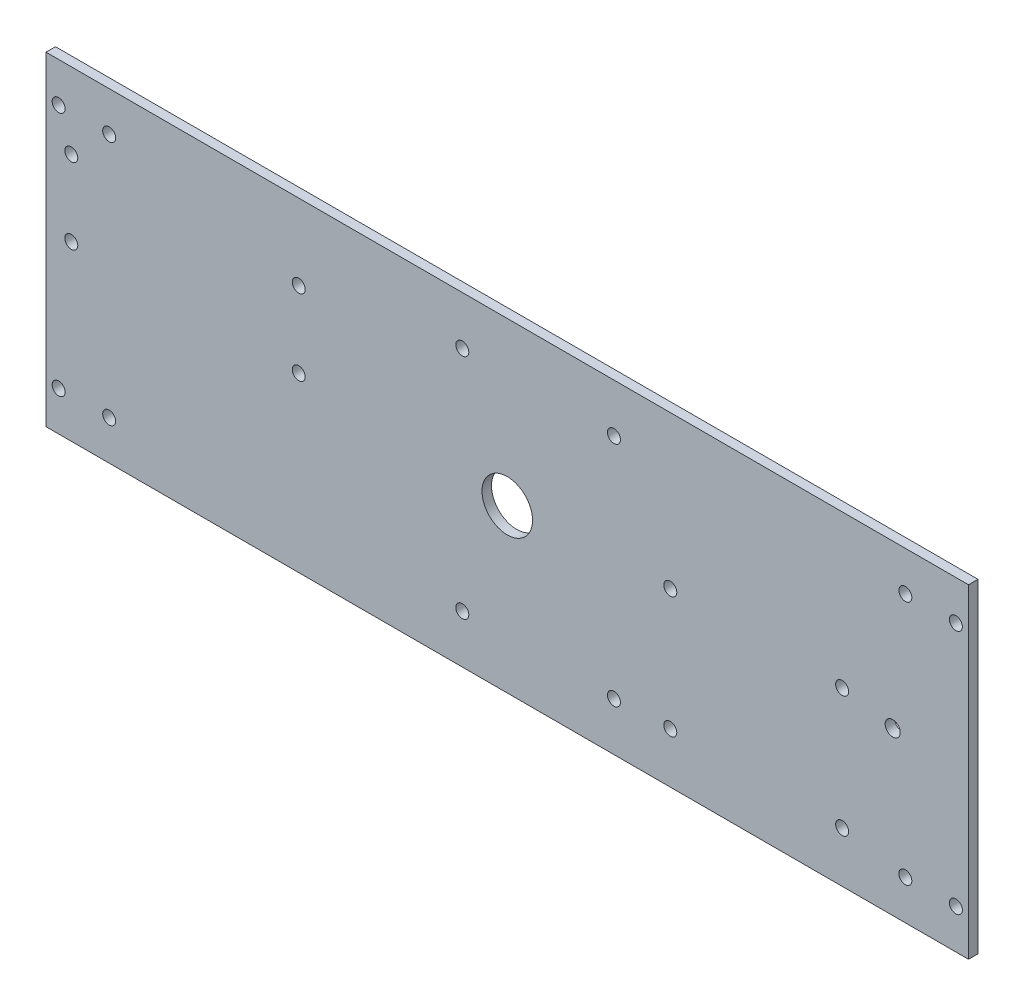
SolidWorks part; units mm, degrees
material "E-Glass Fiber"
ref_plane "Front Plane" through (0, 0, 0) normal (0, 0, 1) x (1, 0, 0)
ref_plane "Top Plane" through (0, 0, 0) normal (0, 1, 0) x (1, 0, 0)
ref_plane "Right Plane" through (0, 0, 0) normal (1, 0, 0) x (0, 0, -1)
sketch "Sketch1" plane through (0, 0, 0) normal (0, 0, 1) x (1, 0, 0)
  line L1 (-115.8875, -40.748) -> (115.8875, -40.748)
  line L2 (-115.8875, -40.748) -> (-115.8875, 40.7479)
  line L3 (-115.8875, 40.7479) -> (115.8875, 40.7479)
  line L4 (115.8875, -40.748) -> (115.8875, 40.7479)
  line L5 (-115.8875, -40.748) -> (115.8875, 40.7479) construction
  line L6 (-115.8875, 40.7479) -> (115.8875, -40.748) construction
  point P0 (0, 0)
  dimension "D1" = 231.775
  dimension "D2" = 81.4959
extrude "Boss-Extrude1" add sketch "Sketch1" along normal blind 2.3813
sketch "Sketch2" plane through (0, 0, 2.3813) normal (0, 0, 1) x (1, 0, 0)
  line L0 (-11.2979, 28.575) -> (26.8021, 28.575) construction
  line L1 (-115.8875, 0) -> (-111.125, 0) construction
  line L2 (115.8875, 0) -> (96.8375, 0) construction
  line L3 (-115.8875, 40.7479) -> (-115.8875, -40.748) construction
  line L4 (-111.125, 0) -> (-111.125, 9.525) construction
  line L5 (-111.125, 9.525) -> (-111.125, 25.4) construction
  line L6 (115.8875, 0) -> (111.125, 0) construction
  line L7 (115.8875, -40.748) -> (115.8875, 40.7479) construction
  line L8 (111.125, 0) -> (111.125, 9.525) construction
  line L9 (111.125, 9.525) -> (111.125, 25.4) construction
  line L10 (-112.7125, 40.7479) -> (-112.7125, 30.8204) construction
  line L11 (115.8875, 40.7479) -> (-115.8875, 40.7479) construction
  line L12 (-112.7125, 30.8204) -> (-100.0125, 30.8204) construction
  line L13 (-112.7125, 30.8204) -> (-115.8875, 30.8204) construction
  dimension "D1" = 38.1
  dimension "D2" = 28.575
  dimension "D3" = 11.2979
  dimension "D4" = 9.525
  dimension "D5" = 25.4
  dimension "D6" = 4.7625
  dimension "D7" = 3.175
  dimension "D8" = 30.8204
  dimension "D9" = 12.7
  dimension "D10" = 19.05
hole_wizard "#4 Clearance Hole1" positions "Sketch4" profile "Sketch5" hole size "#4" standard "ANSI Inch" end condition through all
sketch "Sketch4" plane through (0, 0, 2.3813) normal (0, 0, 1) x (1, 0, 0)
  point P0 (-11.2979, 28.575)
  point P3 (26.8021, 28.575)
sketch "Sketch5" plane through (-11.2979, 28.575, 2.3813) normal (1, 0, 0) x (0, -1, 0)
  line L0 (0, 0) -> (0, 2.3813)
  line L1 (0, 2.3813) -> (1.6319, 2.3813)
  line L2 (1.6319, 2.3813) -> (1.6319, 0)
  line L5 (1.6319, 0) -> (0, 0)
  line L11 (0, -6.35) -> (0, 107.95) construction
  dimension "Thru Hole Dia." = 3.2639
  dimension "Thru Hole Depth" = 2.3813
mirror "Mirror1" about plane through (0, 0, 0) normal (0, 1, 0) of "#4 Clearance Hole1"
hole_wizard "#4 Clearance Hole2" positions "Sketch7" profile "Sketch6" hole size "#4" standard "ANSI Inch"
sketch "Sketch7" plane through (0, 0, 2.3813) normal (0, 0, 1) x (1, 0, 0)
  point P0 (-112.7125, 30.8204)
  point P3 (-100.0125, 30.8204)
sketch "Sketch6" plane through (-112.7125, 30.8204, 2.3813) normal (1, 0, 0) x (0, -1, 0)
  line L0 (0, 0) -> (0, 10.5056)
  line L1 (0, 10.5056) -> (1.6319, 9.525)
  line L2 (1.6319, 9.525) -> (1.6319, 0)
  line L5 (1.6319, 0) -> (0, 0)
  line L10 (0, 10.5056) -> (-1.632, 9.525) construction
  line L11 (0, -6.35) -> (0, 107.95) construction
  dimension "Hole Dia." = 3.2639
  dimension "Hole Depth" = 9.525
  dimension "Drill Angle" = 118
mirror "Mirror2" about plane through (0, 0, 0) normal (1, 0, 0) of "#4 Clearance Hole2"
mirror "Mirror3" about plane through (0, 0, 0) normal (0, 1, 0) of "Mirror2"
hole_wizard "1/2 (0.5) Diameter Hole1" positions "Sketch9" profile "Sketch8" hole size "1/2" standard "ANSI Inch" end condition through all
sketch "Sketch9" plane through (0, 0, 2.3813) normal (0, 0, 1) x (1, 0, 0)
  point P0 (0, 0)
sketch "Sketch8" plane through (0, 0, 2.3813) normal (1, 0, 0) x (0, -1, 0)
  line L0 (0, 0) -> (0, 2.3812)
  line L1 (0, 2.3812) -> (6.35, 2.3812)
  line L2 (6.35, 2.3812) -> (6.35, 0)
  line L5 (6.35, 0) -> (0, 0)
  line L11 (0, -6.35) -> (0, 107.95) construction
  dimension "Thru Hole Dia." = 12.7
  dimension "Thru Hole Depth" = 2.3813
sketch "Sketch10" plane through (0, 0, 2.3813) normal (0, 0, 1) x (1, 0, 0)
  line L0 (-115.8875, 40.7479) -> (-115.8875, -40.748) construction
  line L1 (-109.5375, 21.6979) -> (-52.3875, 21.6979) construction
  line L2 (-109.5375, 21.6979) -> (-109.5375, 2.6479) construction
  line L3 (-109.5375, 2.6479) -> (-52.3875, 2.6479) construction
  line L4 (-52.3875, 21.6979) -> (-52.3875, 2.6479) construction
  line L5 (115.8875, 40.7479) -> (-115.8875, 40.7479) construction
  line L6 (-115.8875, -40.748) -> (115.8875, -40.748) construction
  line L7 (40.9575, -28.048) -> (84.1375, -28.048)
  line L8 (40.9575, -28.048) -> (40.9575, 2.432)
  line L9 (40.9575, 2.432) -> (84.1375, 2.432)
  line L10 (84.1375, -28.048) -> (84.1375, 2.432)
  line L11 (40.9575, -28.048) -> (84.1375, 2.432) construction
  line L12 (40.9575, 2.432) -> (84.1375, -28.048) construction
  line L13 (115.8875, -40.748) -> (115.8875, 40.7479) construction
  point P8 (62.5475, -12.808)
  dimension "D1" = 57.15
  dimension "D2" = 19.05
  dimension "D3" = 6.35
  dimension "D4" = 19.05
  dimension "D5" = 30.48
  dimension "D6" = 43.18
  dimension "D7" = 12.7
  dimension "D8" = 31.75
hole_wizard "#4 Clearance Hole3" positions "Sketch12" profile "Sketch11" hole size "#4" standard "ANSI Inch" end condition through all
sketch "Sketch12" plane through (0, 0, 2.3813) normal (0, 0, 1) x (1, 0, 0)
  point P0 (-109.5375, 21.6979)
  point P3 (-109.5375, 2.6479)
  point P6 (-52.3875, 2.6479)
  point P9 (-52.3875, 21.6979)
  point P13 (40.9575, 2.432)
  point P16 (84.1375, 2.432)
  point P19 (84.1375, -28.048)
  point P22 (40.9575, -28.048)
sketch "Sketch11" plane through (-109.5375, 21.6979, 2.3813) normal (1, 0, 0) x (0, -1, 0)
  line L0 (0, 0) -> (0, 2.3813)
  line L1 (0, 2.3813) -> (1.6319, 2.3813)
  line L2 (1.6319, 2.3813) -> (1.6319, 0)
  line L5 (1.6319, 0) -> (0, 0)
  line L11 (0, -6.35) -> (0, 107.95) construction
  dimension "Thru Hole Dia." = 3.2639
  dimension "Thru Hole Depth" = 2.3813
hole_wizard "#6 Clearance Hole1" positions "Sketch15" profile "Sketch16" hole size "#6" standard "ANSI Inch" end condition through all
sketch "Sketch15" plane through (0, 0, 2.3813) normal (0, 0, 1) x (1, 0, 0)
  point P0 (96.8375, 0)
sketch "Sketch16" plane through (96.8375, 0, 2.3813) normal (1, 0, 0) x (0, -1, 0)
  line L0 (0, 0) -> (0, 2.3812)
  line L1 (0, 2.3812) -> (1.8986, 2.3812)
  line L2 (1.8986, 2.3812) -> (1.8986, 0)
  line L5 (1.8986, 0) -> (0, 0)
  line L11 (0, -6.35) -> (0, 107.95) construction
  dimension "Thru Hole Dia." = 3.7973
  dimension "Thru Hole Depth" = 2.3813
